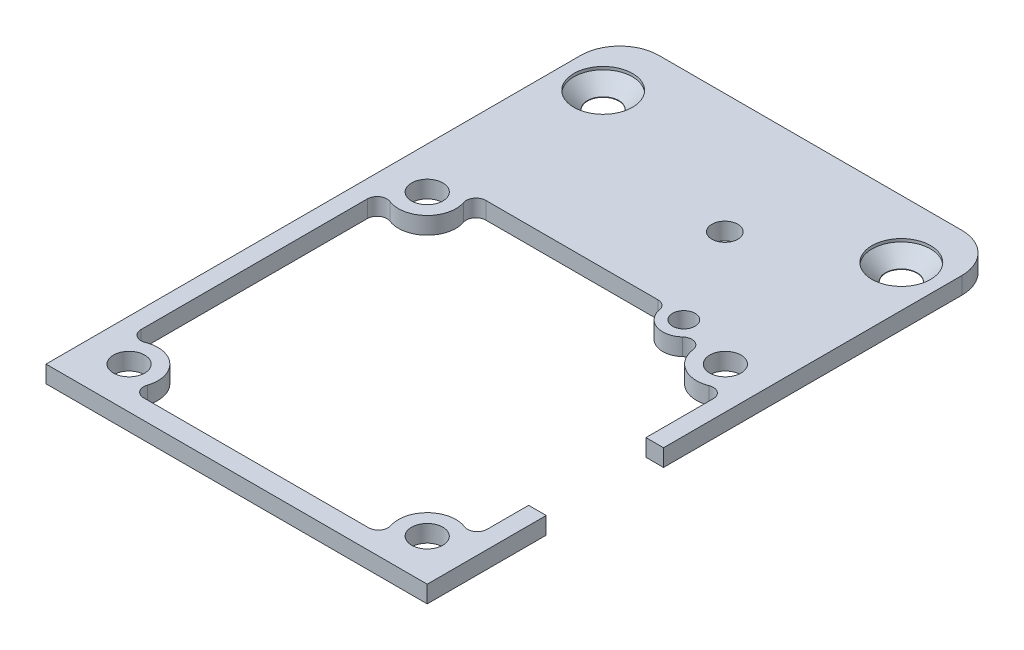
SolidWorks part; units mm, degrees
ref_plane "Front Plane" through (0, 0, 0) normal (0, 0, 1) x (1, 0, 0)
ref_plane "Top Plane" through (0, 0, 0) normal (0, 1, 0) x (1, 0, 0)
ref_plane "Right Plane" through (0, 0, 0) normal (1, 0, 0) x (0, 0, -1)
sketch "Sketch1" plane through (0, 0, 0) normal (0, 1, 0) x (1, 0, 0)
  line L0 (-15.5, 39.2) -> (15.5, 39.2)
  line L1 (-18.2, 15) -> (-18.2, -15) construction
  line L2 (17.7, -17.4996) -> (-17.7, -17.4996)
  line L3 (17.7, -17.4996) -> (17.7, 17.4996)
  line L4 (17.7, 17.4996) -> (-17.7, 17.4996)
  line L5 (-17.7, -17.4996) -> (-17.7, 17.4996)
  line L6 (17.7, -17.4996) -> (-17.7, 17.4996) construction
  line L7 (-19.5, 35.2) -> (-19.5, -19.5)
  line L8 (-19.5, -19.5) -> (19.5, -19.5)
  line L9 (19.5, -19.5) -> (19.5, 35.2)
  line L10 (17.7, 17.4996) -> (-17.7, -17.4996) construction
  line L11 (-15.25, 15.25) -> (-15.25, 17.9996) construction
  line L12 (11.35, 17.05) -> (11.35, 17.4996)
  line L13 (7.05, 17.05) -> (7.05, 17.4996)
  arc A0 (19.5, 35.2) -> (15.5, 39.2) centre (15.5, 35.2) ccw construction
  arc A1 (-15.5, 39.2) -> (-19.5, 35.2) centre (-15.5, 35.2) ccw construction
  arc A2 (19.5, 35.2) -> (15.5, 39.2) centre (15.5, 35.2) ccw
  arc A3 (-15.5, 39.2) -> (-19.5, 35.2) centre (-15.5, 35.2) ccw
  circle A4 centre (-15.25, -15.25) radius 1.6 construction
  circle A5 centre (15.25, -15.25) radius 1.6 construction
  circle A6 centre (-15.25, 15.25) radius 1.6 construction
  circle A7 centre (15.25, 15.25) radius 1.6 construction
  circle A8 centre (-15.25, 33.25) radius 1.6 construction
  circle A9 centre (15.25, 33.25) radius 1.6 construction
  circle A10 centre (-15.25, -15.25) radius 1.6
  circle A11 centre (15.25, -15.25) radius 1.6
  circle A12 centre (-15.25, 15.25) radius 1.6
  circle A13 centre (15.25, 15.25) radius 1.6
  circle A14 centre (-15.25, 33.25) radius 1.6
  circle A15 centre (15.25, 33.25) radius 1.6
  arc A16 (-15.2, 18) -> (-18.2, 15) centre (-15.2, 15) ccw construction
  circle A17 centre (-15.25, 15.25) radius 2.95
  circle A18 centre (15.25, 15.25) radius 2.95
  circle A19 centre (-15.25, -15.25) radius 2.95
  circle A20 centre (15.25, -15.25) radius 2.95
  circle A21 centre (3.5, 26.95) radius 1.33 construction
  circle A22 centre (9.2, 17.05) radius 2.15
  circle A23 centre (9.2, 17.05) radius 1.15
  circle A24 centre (9.2, 17.05) radius 0.9 construction
  circle A25 centre (3.5, 26.95) radius 1.33
  circle A26 centre (11.334, 14.733) radius 1
  point P29 (0, 0)
  dimension "D3" = 2.3
  dimension "D4" = 1
  dimension "D5" = 2
  dimension "D1" = 0.5
  dimension "D2" = 0.5
extrude "Base shape" add sketch "Sketch1" along normal blind 1.75 contours L0 A3 L7 L8 L9 A2 A20 L3 L2 A19 L5 A17 L4 A18 A15 A14 | A17 L4 L5 | L4 A17 L5 A12 | L5 A17 | L4 A17 | L3 A18 L4 A13 | L3 A18 | L4 A18 | L2 A19 L5 A10 | L2 A19 | L5 A19 | A19 L5 L2 | L2 A20 L3 A11 | L3 A20 | L2 A20 | A20 L2 L3 | A18 L3 L4 | A23 L4 A22 | A23 L4 A22 | A22 L4 L13 | A22 L12 L4 | A26 A18 L4 L12 A22 region at (-0.0683, 0, -21.4041) region at (17.5279, 0, 17.307) region at (15.25, 0, 17.7828) region at (15.25, 0, 17.4246) region at (17.9015, 0, 15.25) region at (-15.25, 0, 17.7828) region at (-15.25, 0, 17.4246) region at (14.5952, 0, -12.4505) region at (17.9015, 0, -15.25) region at (-17.5279, 0, 17.307) region at (17.5279, 0, -17.307) region at (11.9929, 0, -16.5859) region at (-17.9015, 0, 15.25) region at (15.25, 0, -17.7828) region at (8.3568, 0, -15.127) region at (-17.9015, 0, -15.25) region at (-17.625, 0, -15.25) region at (11.3358, 0, -17.3874) region at (7.0642, 0, -17.3874) region at (-17.5279, 0, -17.307) region at (9.2, 0, -18.3154) region at (-15.25, 0, -17.7828)
fillet "Milling fillets" radius 1 8 edges at (-17.7, 0.875, 13.6068) (-13.3416, 0.875, 17.4996) (13.3416, 0.875, 17.4996) (17.7, 0.875, 13.6068) (17.7, 0.875, -13.6068) (-13.3416, 0.875, -17.4996) (-17.7, 0.875, -13.6068) (7.05, 0.875, -17.4996)
sketch "Sketch3" plane through (0, 1.75, 0) normal (0, 1, 0) x (1, 0, 0)
  circle A0 centre (-15.25, 33.25) radius 3
  circle A1 centre (15.25, 33.25) radius 3
  dimension "D1" = 6
extrude "Screw head cut" cut sketch "Sketch3" against normal blind 0.3
chamfer "Screw head chamfer" distance 1.4 angle 45 2 edges at (15.25, 1.45, -31.65) (-15.25, 1.45, -31.65)
sketch "Sketch4" plane through (19.5, 0, 0) normal (1, 0, 0) x (0, 0, -1)
  line L0 (4.175, 1) -> (4.175, 0.2) construction
  line L1 (4.175, 1) -> (4.175, 0.2)
  line L2 (-6.825, 1) -> (-6.825, 0.2) construction
  line L3 (-6.825, 1) -> (-6.825, 0.2)
  line L4 (-6.825, 1) -> (4.175, 0.2) construction
  line L5 (-19.5, 0) -> (35.2, 0) construction
  line L6 (4.675, 0) -> (-7.325, 0)
  line L7 (4.675, 0) -> (4.675, 1.2)
  line L8 (4.675, 1.2) -> (-7.325, 1.2)
  line L9 (-7.325, 0) -> (-7.325, 1.2)
  line L10 (4.675, 0) -> (-7.325, 1.2) construction
  line L11 (4.675, 1.2) -> (-7.325, 0) construction
  line L12 (-19.5, 1.75) -> (35.2, 1.75) construction
  line L13 (4.675, 1.2) -> (-7.325, 1.2)
  line L14 (4.675, 1.2) -> (4.675, 1.75)
  line L15 (4.675, 1.75) -> (-7.325, 1.75)
  line L16 (-7.325, 1.2) -> (-7.325, 1.75)
  point P4 (-1.325, 0.6)
  line M6 (35.2, 1.75) -> (-19.5, 1.75)
  dimension "D1" = 0.5
extrude "Cut-Extrude1" cut sketch "Sketch4" against normal up to next contours L9 L7 L8 | L16 L8 L14 M6 region at (19.5, 0.6, 1.325) region at (19.5, 1.475, 1.325)
